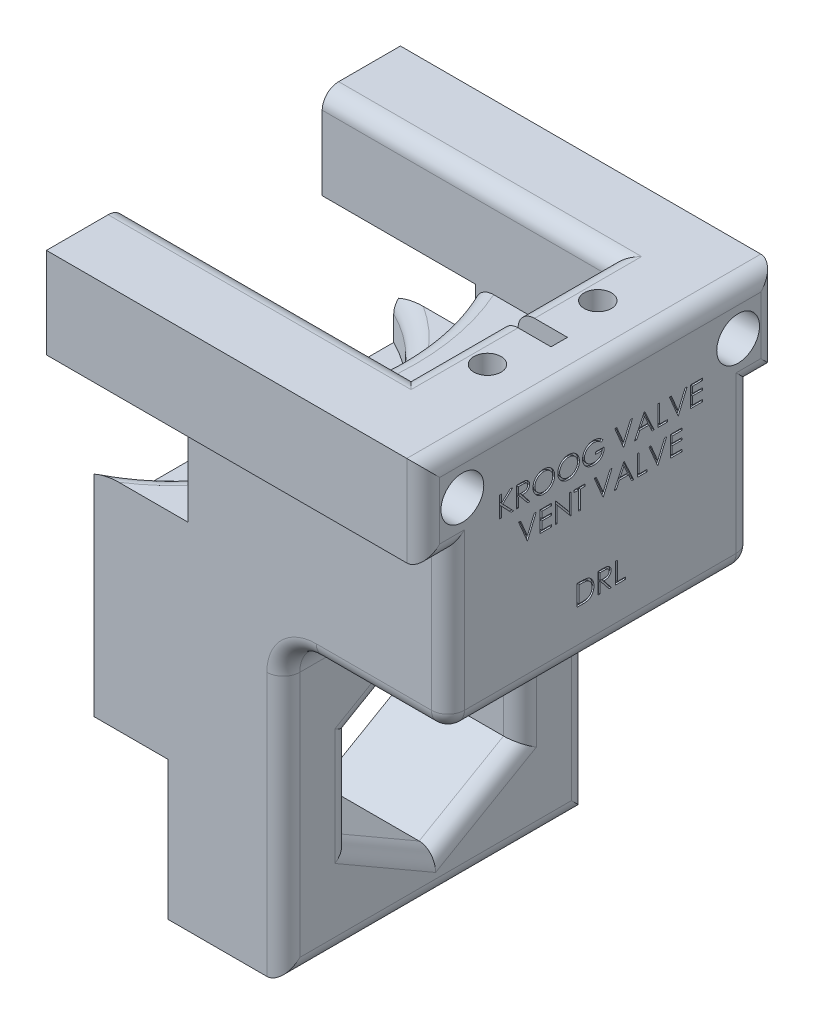
SolidWorks part; units mm, degrees
note: The reader was unsure of these and kept them because the rebuilt part matched: shared geometry of "Sketch5<3>".
material "ABS"
ref_plane "Front Plane" through (0, 0, 0) normal (0, 0, 1) x (1, 0, 0)
ref_plane "Top Plane" through (0, 0, 0) normal (0, 1, 0) x (1, 0, 0)
ref_plane "Right Plane" through (0, 0, 0) normal (1, 0, 0) x (0, 0, -1)
sketch "Sketch2" plane through (0, 0, 0) normal (1, 0, 0) x (0, 0, -1)
  line L1 (0, 15.0313) -> (-13.0175, 7.5157)
  line L2 (-13.0175, 7.5157) -> (-13.0175, -7.5157)
  line L3 (-13.0175, -7.5157) -> (0, -15.0313)
  line L4 (0, -15.0313) -> (13.0175, -7.5157)
  line L5 (13.0175, -7.5157) -> (13.0175, 7.5157)
  line L6 (13.0175, 7.5157) -> (0, 15.0313)
  line L7 (-23.495, -21.3813) -> (23.495, -21.3813)
  line L8 (-23.495, -21.3813) -> (-23.495, 48.4687)
  line L9 (-23.495, 62.4387) -> (23.495, 62.4387)
  line L10 (23.495, -21.3813) -> (23.495, 48.4687)
  line L11 (-23.495, 62.4387) -> (-27.305, 62.4387)
  line L13 (-23.495, 48.4687) -> (-27.305, 48.4687)
  line L14 (-27.305, 62.4387) -> (-27.305, 48.4687)
  line L15 (23.495, 62.4387) -> (27.305, 62.4387)
  line L17 (23.495, 48.4687) -> (27.305, 48.4687)
  line L18 (27.305, 62.4387) -> (27.305, 48.4687)
  circle A0 centre (0, 0) radius 13.0175 construction
  point P13 (0, -21.3813)
  dimension "D1" = 26.035
  dimension "D2" = 6.35
  dimension "D3" = 46.99
  dimension "D4" = 83.82
  dimension "D5" = 13.97
  dimension "D6" = 3.81
extrude "Boss-Extrude1" add sketch "Sketch2" along normal blind 17.78
sketch "Sketch4" plane through (0, 0, 0) normal (-1, 0, 0) x (0, 0, 1)
  line L0 (-23.495, -21.3813) -> (-23.495, 48.4687) construction
  line L1 (-23.495, 16.3013) -> (23.495, 16.3013)
  line L2 (-23.495, 16.3013) -> (-23.495, 48.4687)
  line L4 (23.495, 16.3013) -> (23.495, 48.4687)
  line L5 (27.305, 62.4387) -> (27.305, 48.4687) construction
  line L6 (27.305, 48.4687) -> (23.495, 48.4687) construction
  line L7 (-23.495, 48.4687) -> (-27.305, 48.4687) construction
  line L8 (-27.305, 48.4687) -> (-27.305, 62.4387) construction
  line L9 (-27.305, 62.4387) -> (27.305, 62.4387) construction
  line L10 (27.305, 62.4387) -> (27.305, 48.4687)
  line L11 (27.305, 48.4687) -> (23.495, 48.4687)
  line L12 (-23.495, 48.4687) -> (-27.305, 48.4687)
  line L13 (-27.305, 48.4687) -> (-27.305, 62.4387)
  line L14 (-27.305, 62.4387) -> (27.305, 62.4387)
  line L15 (23.495, 48.4687) -> (23.495, -21.3813) construction
  dimension "D1" = 1.27
extrude "Boss-Extrude2" add sketch "Sketch4" along normal blind 11.43
sketch "Sketch5" plane through (0, 62.4387, 0) normal (0, 1, 0) x (1, 0, 0)
  line L0 (0, 0) -> (-22.7305, 0) construction
  line L2 (-11.43, -27.305) -> (-11.43, 27.305) construction
  circle A0 centre (-22.7305, 0) radius 34.925
  circle A1 centre (-22.7305, 0) radius 25.4
  dimension "D2" = 69.85
  dimension "D3" = 50.8
  dimension "D1" = 11.3005
extrude "Cut-Extrude1" cut sketch "Sketch5" against normal blind 15.24 from offset 13.97 offset against normal yes
extrude "Cut-Extrude2" cut sketch "Sketch5<3>" against normal blind 6.35 from surface
sketch "Sketch5<3>" plane through (0, 62.4387, 0) normal (0, 1, 0) x (1, 0, 0) same geometry as "Sketch5"
sketch "Sketch6" plane through (-11.43, 0, 0) normal (-1, 0, 0) x (0, 0, 1)
  line L4 (-27.305, 48.4687) -> (27.305, 48.4687)
  line L19 (-27.305, 48.4687) -> (27.305, 48.4687)
  line L23 (-27.305, 62.4387) -> (-27.305, 48.4687)
  line L25 (-27.305, 62.4387) -> (-27.305, 48.4687)
  line L27 (27.305, 48.4687) -> (27.305, 62.4387)
  line L28 (27.305, 48.4687) -> (27.305, 62.4387)
  line L29 (27.305, 62.4387) -> (-27.305, 62.4387)
  line L30 (27.305, 62.4387) -> (-27.305, 62.4387)
  dimension "D1" = 0
extrude "Boss-Extrude3" add sketch "Sketch6" along normal blind 3.5301
sketch "Sketch11" plane through (17.78, 0, 0) normal (1, 0, 0) x (0, 0, -1)
  line L0 (23.495, -21.3813) -> (23.495, 48.4687) construction
  line L2 (-23.495, 48.4687) -> (-23.495, 24.3387)
  line L3 (-23.495, 24.3387) -> (23.495, 24.3387)
  line L4 (23.495, 48.4687) -> (23.495, 24.3387)
  line L5 (-23.495, 48.4687) -> (-23.495, -21.3813) construction
  line L6 (23.495, 48.4687) -> (27.305, 48.4687) construction
  line L7 (27.305, 48.4687) -> (27.305, 62.4387) construction
  line L8 (-27.305, 48.4687) -> (-23.495, 48.4687) construction
  line L9 (-27.305, 62.4387) -> (-27.305, 48.4687) construction
  line L10 (27.305, 62.4387) -> (-27.305, 62.4387) construction
  line L11 (23.495, 48.4687) -> (27.305, 48.4687)
  line L12 (27.305, 48.4687) -> (27.305, 62.4387)
  line L13 (-27.305, 48.4687) -> (-23.495, 48.4687)
  line L14 (-27.305, 62.4387) -> (-27.305, 48.4687)
  line L15 (27.305, 62.4387) -> (-27.305, 62.4387)
  dimension "D1" = 38.1
extrude "Boss-Extrude4" add sketch "Sketch11" along normal blind 25.4
sketch "Sketch7" plane through (0, 62.4387, 0) normal (0, 1, 0) x (1, 0, 0)
  line L1 (-14.9601, 15.24) -> (29.2359, 15.24)
  line L2 (-14.9601, 15.24) -> (-14.9601, -15.24)
  line L3 (-14.9601, -15.24) -> (29.2359, -15.24)
  line L4 (29.2359, 15.24) -> (29.2359, -15.24)
  line L5 (-14.9601, -27.305) -> (-14.9601, 27.305) construction
  point P4 (0, 0)
  point P6 (29.2359, 0)
  dimension "D1" = 30.48
  dimension "D2" = 44.196
extrude "Cut-Extrude3" cut sketch "Sketch7" against normal up to surface (13.97 mm away) up to face at (19.7631, 48.4687, 0)
sketch "Sketch8" plane through (0, 62.4387, 0) normal (0, 1, 0) x (1, 0, 0)
  line L0 (29.2359, -15.24) -> (29.2359, 15.24) construction
  line L1 (29.2359, -1.27) -> (36.8559, -1.27)
  line L2 (29.2359, -1.27) -> (29.2359, 1.27)
  line L3 (29.2359, 1.27) -> (36.8559, 1.27)
  line L4 (36.8559, -1.27) -> (36.8559, 1.27)
  point P6 (33.0459, -1.27)
  point P7 (29.2359, 0)
  dimension "D1" = 2.54
  dimension "D2" = 7.62
extrude "Cut-Extrude4" cut sketch "Sketch8" against normal blind 2.54
sketch "Sketch9" plane through (0, 62.4387, 0) normal (0, 1, 0) x (1, 0, 0)
  line L0 (17.78, 23.495) -> (17.78, -23.495) construction
  line L1 (-14.9601, -23.495) -> (17.78, -23.495) construction
  line L2 (0, 0) -> (17.78, 0) construction
  line L4 (43.18, 27.305) -> (43.18, -27.305) construction
  circle A0 centre (34.29, -8.509) radius 1.27
  circle A1 centre (34.29, 8.509) radius 1.27
  point P0 (34.29, -8.509)
  point P9 (34.29, 8.509)
  dimension "D3" = 2.54
  dimension "D1" = 8.89
  dimension "D2" = 14.986
hole_wizard "Tap Drill for M5x0.8 Tap1" positions "Sketch9" profile "Sketch10" hole size "M5x0.8" standard "ANSI Metric"
sketch "Sketch10" plane through (34.29, 62.4387, 8.509) normal (1, 0, 0) x (0, 0, 1)
  line L0 (0, 0) -> (0, 9.1358)
  line L1 (0, 9.1358) -> (2.1, 7.874)
  line L2 (2.1, 7.874) -> (2.1, 0)
  line L5 (2.1, 0) -> (0, 0)
  line L10 (0, 9.1358) -> (-2.1, 7.874) construction
  line L11 (0, -6.35) -> (0, 107.95) construction
  dimension "Hole Dia." = 4.2
  dimension "Hole Depth" = 7.874
  dimension "Drill Angle" = 118
sketch "Sketch12" plane through (0, 0, 0) normal (-1, 0, 0) x (0, 0, 1)
  line L0 (-23.495, 16.3013) -> (23.495, 16.3013) construction
  line L1 (-23.495, 16.3013) -> (23.495, 16.3013)
  line L2 (-15.494, 0) -> (-23.495, 0)
  line L3 (-23.495, -21.3813) -> (-23.495, 16.3013) construction
  line L4 (-23.495, 0) -> (-23.495, 16.3013)
  line L5 (15.494, 0) -> (23.495, 0)
  line L8 (23.495, 16.3013) -> (23.495, -21.3813) construction
  line L9 (23.495, 0) -> (23.495, 16.3013)
  arc A0 (-15.494, 0) -> (15.494, 0) centre (0, 0) cw
  dimension "D1" = 15.494
extrude "Boss-Extrude5" add sketch "Sketch12" along normal up to surface (11.43 mm away) up to face at (-11.43, 27.4093, 0)
fillet "Fillet3" radius 2.54 2 edges at (2.6695, 33.2287, 0) (12.1945, 48.4687, 0)
fillet "Fillet4" radius 2.54 3 edges at (-5.715, 0, -15.494) (-5.715, 0, 15.494) (-11.43, 15.494, 0)
fillet "Fillet5" radius 5.08 1 edges at (17.78, 24.3387, 0)
fillet "Fillet6" radius 2.54 20 edges at (33.02, 24.3387, 23.495) (19.2679, 22.8508, 23.495) (33.02, 24.3387, -23.495) (19.2679, 22.8508, -23.495) (17.78, -21.3813, 0) (17.78, -1.0613, 23.495) (17.78, -1.0613, -23.495) (17.78, 11.2735, 6.5087) (17.78, 0, 13.0175) (17.78, -11.2735, 6.5087) (17.78, -11.2735, -6.5087) (17.78, 0, -13.0175) (17.78, 11.2735, -6.5087) (43.18, 36.4037, -23.495) (43.18, 24.3387, 0) (43.18, 36.4037, 23.495) (43.18, 48.4687, -25.4) (43.18, 55.4537, 27.305) (43.18, 62.4387, 0) (43.18, 55.4537, -27.305)
fillet "Fillet7" radius 2.54 4 edges at (29.2359, 62.4387, 8.255) (7.1379, 62.4387, 15.24) (29.2359, 62.4387, -8.255) (7.1379, 62.4387, -15.24)
sketch "Sketch15" plane through (-14.9601, 0, 0) normal (-1, 0, 0) x (0, 0, 1)
  line L0 (-27.305, 55.4537) -> (-15.24, 55.4537) construction
  line L1 (-27.305, 62.4387) -> (-27.305, 48.4687) construction
  line L2 (-15.24, 48.4687) -> (-15.24, 59.8987) construction
  line L3 (-21.2725, 48.4687) -> (-21.2725, 62.4387) construction
  line L4 (-27.305, 48.4687) -> (-15.24, 48.4687) construction
  line L5 (-17.78, 62.4387) -> (-27.305, 62.4387) construction
  line L6 (0, 0) -> (0, 62.4387) construction
  line L7 (1.27, 62.4387) -> (-1.27, 62.4387) construction
  circle A0 centre (-21.2725, 55.4537) radius 3.302
  circle A1 centre (21.2725, 55.4537) radius 3.302
  dimension "D1" = 6.604
extrude "Cut-Extrude7" cut sketch "Sketch15" against normal through all
sketch "Sketch16" plane through (43.18, 0, 0) normal (1, 0, 0) x (0, 0, -1)
  line L0 (-20.955, 49.7387) -> (20.955, 49.7387) construction
  line L1 (-20.955, 44.6587) -> (20.955, 44.6587) construction
  line L2 (-20.955, 51.0087) -> (-20.955, 26.8787) construction
  line L3 (20.955, 26.8787) -> (20.955, 51.0087) construction
  line L4 (-20.955, 31.9587) -> (20.955, 31.9587) construction
  line L5 (-20.955, 26.8787) -> (20.955, 26.8787) construction
  text T0 "KROOG VALVE"
  text T1 "VENT VALVE"
  text T2 "DRL"
  dimension "D1" = 5.08
  dimension "D2" = 12.7
  dimension "D3" = 5.08
extrude "Cut-Extrude8" cut sketch "Sketch16" against normal blind 0.254
